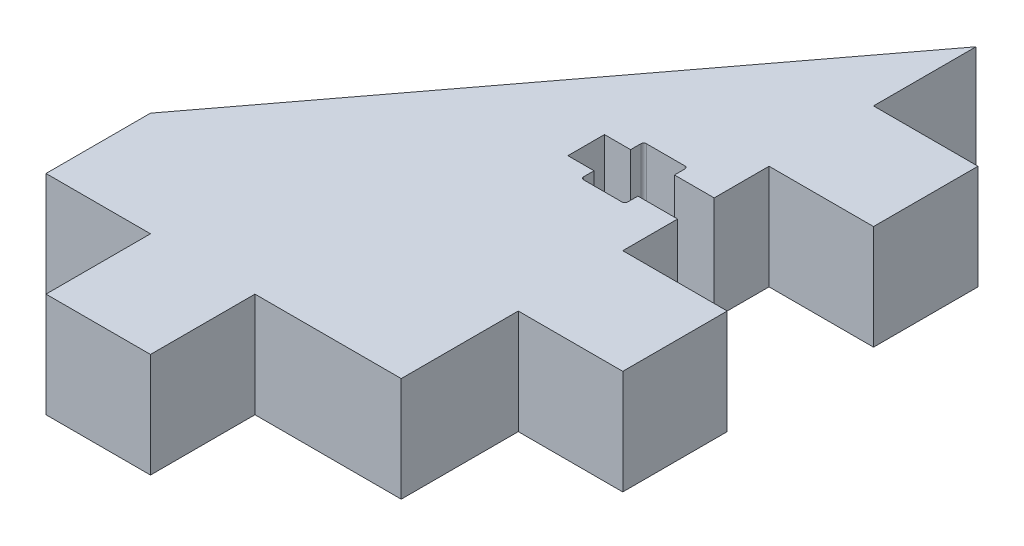
SolidWorks part; units mm, degrees
ref_plane "Front Plane" through (0, 0, 0) normal (0, 0, 1) x (1, 0, 0)
ref_plane "Top Plane" through (0, 0, 0) normal (0, 1, 0) x (1, 0, 0)
ref_plane "Right Plane" through (0, 0, 0) normal (1, 0, 0) x (0, 0, -1)
sketch "Sketch1" plane through (0, 0, 0) normal (0, 1, 0) x (1, 0, 0)
  line L0 (0, 0) -> (-14, 0)
  line L1 (-14, 0) -> (-14, -10)
  line L2 (-14, -10) -> (-24, -10)
  line L3 (-24, -10) -> (-24, 0)
  line L4 (-24, 0) -> (-34, 0)
  line L5 (-34, 0) -> (-34, 10)
  line L6 (-34, 10) -> (0, 55)
  line L7 (0, 55) -> (0, 45.2)
  line L8 (0, 45.2) -> (10, 45.2)
  line L9 (10, 45.2) -> (10, 35.2)
  line L10 (10, 35.2) -> (0, 35.2)
  line L11 (0, 35.2) -> (0, 21.2)
  line L12 (-24, 0) -> (-14, 0) construction
  line L13 (-19, 0) -> (-19, -10) construction
  line L14 (0, 16.2) -> (0, 11.2) construction
  line L15 (5, 11.2) -> (5, 21.2) construction
  line L24 (0, 21.2) -> (10, 21.2)
  line L25 (10, 21.2) -> (10, 11.2)
  line L26 (10, 11.2) -> (0, 11.2)
  line L27 (0, 11.2) -> (0, 0)
  line L32 (10, 40.2) -> (0, 40.2) construction
  line L33 (0, 40.2) -> (0, 35.2) construction
  line L34 (10, 16.2) -> (0, 16.2) construction
  line L35 (0, 16.2) -> (0, 21.2) construction
  dimension "D2" = 10
  dimension "D3" = 10
  dimension "D7" = 10
  dimension "D8" = 10
  dimension "D10" = 10
  dimension "D11" = 10
  dimension "D12" = 10
  dimension "D9" = 55
  dimension "D5" = 16.2
  dimension "D13" = 24
  dimension "D4" = 24
  dimension "D6" = 24
extrude "Boss-Extrude1" add sketch "Sketch1" along normal blind 10
sketch "Sketch2" [suppressed] plane through (0, 8, 0) normal (0, 1, 0) x (1, 0, 0)
  line L0 (0, 29.9) -> (0, 25.9) construction
  line L1 (0, 27.9) -> (-7.2, 27.9) construction
  line L2 (-7.2, 25.9) -> (-7.2, 29.9) construction
  line L3 (7.5, 36.4) -> (7.5, 20.4) construction
  line L4 (0, 36.4) -> (7.5, 36.4) construction
  line L5 (0, 27.9) -> (7.5, 27.9) construction
sketch "Sketch3" plane through (0, 10, 0) normal (0, 1, 0) x (1, 0, 0)
  line L0 (0, 28.2) -> (-10.5, 28.2) construction
  line L1 (0, 21.2) -> (0, 35.2) construction
  line L2 (-10.5, 29.95) -> (-8, 29.95)
  line L3 (-8, 29.95) -> (-8, 30.95)
  line L4 (-7.75, 31.2) -> (-4.05, 31.2)
  line L5 (-3.8, 30.95) -> (-3.8, 29.95)
  line L6 (-3.8, 29.95) -> (0, 29.95)
  line L7 (0, 29.95) -> (0, 26.45)
  line L8 (-10.5, 29.95) -> (-10.5, 26.45)
  line L9 (-3.8, 26.45) -> (0, 26.45)
  line L10 (-3.8, 25.45) -> (-3.8, 26.45)
  line L11 (-7.75, 25.2) -> (-4.05, 25.2)
  line L12 (-8, 26.45) -> (-8, 25.45)
  line L13 (-10.5, 26.45) -> (-8, 26.45)
  arc A0 (-8, 30.95) -> (-7.75, 31.2) centre (-7.75, 30.95) cw
  arc A1 (-4.05, 31.2) -> (-3.8, 30.95) centre (-4.05, 30.95) cw
  arc A2 (-4.05, 25.2) -> (-3.8, 25.45) centre (-4.05, 25.45) ccw
  arc A3 (-8, 25.45) -> (-7.75, 25.2) centre (-7.75, 25.45) ccw
  point P12 (-8, 31.2)
  point P15 (-3.8, 31.2)
  point P26 (-3.8, 25.2)
  point P27 (-8, 25.2)
  dimension "D7" = 0.25
  dimension "D1" = 10.5
  dimension "D3" = 1.75
  dimension "D2" = 8
  dimension "D4" = 4.2
  dimension "D5" = 3
  dimension "D6" = 1.75
extrude "Cut-Extrude1" cut sketch "Sketch3" against normal through all
equation "\"Y-ROD-SPACING\"=75"
equation "\"Y-BED-OFFSET\"=2"
equation "\"Y-BED-ROD-INSET\"=3.5"
equation "\"T-SLOT-NUT-FILLET-RADIUS\"=0.25"
equation "\"T-SLOT-SCREW-SHAFT-RADIUS\"=1.75"
equation "\"T-SLOT-SCREW-SHAFT-CUTOUT-LENGTH\"=10.5"
equation "\"T-SLOT-NUT-DEPTH\"=4.2"
equation "\"T-SLOT-NUT-WIDTH\"=3"
equation "\"T-SLOT-NUT-END-DISTANCE\"=8"
equation "\"ACRYLIC-TAB-CUTOUT-SIZE\"=\"ACRYLIC-THICKNESS\"+\"ACRYLIC-TAB-TOLERANCE\"*2"
equation "\"ACRYLIC-TAB-WIDTH\"=\"ACRYLIC-THICKNESS\""
equation "\"ACRYLIC-M3-HOLE\"=3.1"
equation "\"SMOOTHROD-CAP-SCREW-DISTANCE\"=20"
equation "\"FRAME-WIDTH-INNER\"=370"
equation "\"NEMA17-HOLE-SPACING\"=31"
equation "\"NEMA17-CENTRAL-CUTOUT\"=22.5"
equation "\"D3@Sketch1\"=\"ACRYLIC-TAB-WIDTH\""
equation "\"D12@Sketch1\"=\"ACRYLIC-TAB-WIDTH\""
equation "\"D2@Sketch1\"=\"ACRYLIC-TAB-WIDTH\""
equation "\"D11@Sketch1\"=\"ACRYLIC-TAB-WIDTH\""
equation "\"D1@Sketch1\"=\"ACRYLIC-TAB-WIDTH\""
equation "\"D10@Sketch1\"=\"ACRYLIC-TAB-WIDTH\""
equation "\"Z-BRACKET-REACH\"=55"
equation "\"D9@Sketch1\"=\"Z-BRACKET-REACH\""
equation "\"D6@Sketch3\"=\"T-SLOT-SCREW-SHAFT-RADIUS\""
equation "\"D3@Sketch3\"=\"T-SLOT-SCREW-SHAFT-RADIUS\""
equation "\"D4@Sketch3\"=\"T-SLOT-NUT-DEPTH\""
equation "\"D7@Sketch3\"=\"T-SLOT-NUT-FILLET-RADIUS\""
equation "\"D1@Sketch3\"=\"T-SLOT-SCREW-SHAFT-CUTOUT-LENGTH\""
equation "\"D5@Sketch3\"=\"T-SLOT-NUT-WIDTH\""
equation "\"D2@Sketch3\"=\"T-SLOT-NUT-END-DISTANCE\""
equation "\"X-ROD-SPACING\"=45"
equation "\"Z-ROD-SPACING\"=17.5"
equation "\"ACRYLIC-THICKNESS\"=10"
equation "\"ACRYLIC-THICKNESS2\"=4.5"
equation "\"TOP-BRACKET-SPACING\"=40"
equation "\"SMOOTHROD-X-LENGTH\"=350"
equation "\"SMOOTHROD-Y-LENGTH\"=350"
equation "\"SMOOTHROD-Z-LENGTH\"=350"
equation "\"SMOOTHROD-TIGHTENING-HEADROOM\"=.25"
equation "\"LEADSCREW-Z-LENGTH\"=300"
equation "\"SCREW-LENGTH-FRAME\"=\"ACRYLIC-THICKNESS\" + 10"
equation "\"SCREW-HEAD-RADIUS\"=6"
equation "\"PRINTED-X-SMOOTHROD-DIAMETER\"=8.2"
equation "\"PRINTED-X-SMOOTHROD-CUTOUT\"=10"
equation "\"PRINTED-X-BASE-HEIGHT\"=10"
equation "\"PRINTED-LM8UU-CUTOUT-SIZE\"=15.25"
equation "\"PRINTED-LM8UU-CUTOUT-LENGTH\"=24.5"
equation "\"PRINTED-X-IDLER-HEIGHT\"=16"
equation "\"PSU-MOUNTING-WIDTH\"=95"
equation "\"PSU-MOUNTING-HEIGHT\"=177"
equation "\"D1@Boss-Extrude1\"=\"ACRYLIC-THICKNESS\""
